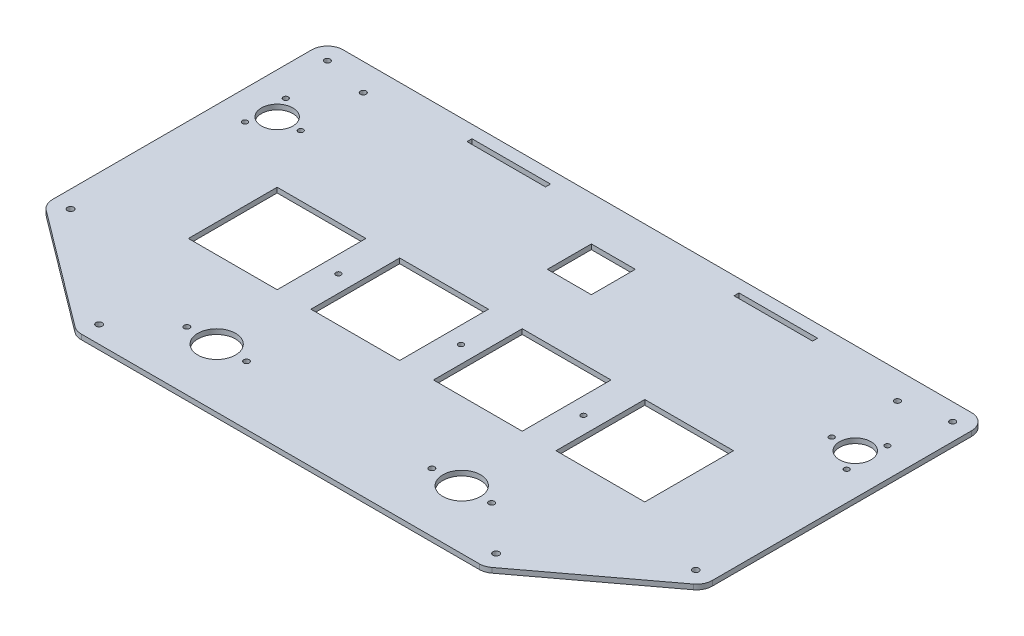
SolidWorks part; units mm, degrees
ref_plane "Front Plane" through (0, 0, 0) normal (0, 0, 1) x (1, 0, 0)
ref_plane "Top Plane" through (0, 0, 0) normal (0, 1, 0) x (1, 0, 0)
ref_plane "Right Plane" through (0, 0, 0) normal (1, 0, 0) x (0, 0, -1)
sketch "Sketch1" plane through (0, 0, 0) normal (0, 1, 0) x (1, 0, 0)
  line L0 (210, 240) -> (210, 0) construction
  line L1 (0, 0) -> (420, 0)
  line L2 (0, 0) -> (0, 240)
  line L3 (0, 240) -> (420, 240)
  line L4 (420, 0) -> (420, 240)
  line L5 (62, 115) -> (124, 115) construction
  line L6 (193, 215) -> (227, 215) construction
  line L7 (193, 215) -> (193, 181) construction
  line L8 (193, 181) -> (227, 181) construction
  line L9 (227, 215) -> (227, 181) construction
  line L10 (62, 84) -> (124, 84) construction
  line L11 (62, 84) -> (62, 146) construction
  line L12 (62, 146) -> (124, 146) construction
  line L13 (124, 84) -> (124, 146) construction
  line L14 (93, 146) -> (93, 84) construction
  line L15 (124, 84) -> (140, 84) construction
  line L16 (140, 84) -> (202, 84) construction
  line L17 (140, 84) -> (140, 146) construction
  line L18 (140, 146) -> (202, 146) construction
  line L19 (202, 84) -> (202, 146) construction
  line L20 (218, 84) -> (280, 84) construction
  line L21 (218, 84) -> (218, 146) construction
  line L22 (218, 146) -> (280, 146) construction
  line L23 (280, 84) -> (280, 146) construction
  line L24 (296, 84) -> (358, 84) construction
  line L25 (296, 84) -> (296, 146) construction
  line L26 (296, 146) -> (358, 146) construction
  line L27 (358, 84) -> (358, 146) construction
  line L28 (202, 84) -> (218, 84) construction
  line L29 (280, 84) -> (296, 84) construction
  line L30 (193, 198) -> (227, 198) construction
  line L31 (132, 84) -> (132, 54) construction
  line L32 (107, 21) -> (157, 21) construction
  line L33 (107, 21) -> (107, 54) construction
  line L34 (107, 54) -> (157, 54) construction
  line L35 (157, 21) -> (157, 54) construction
  line L36 (107, 37.5) -> (157, 37.5) construction
  line L37 (313, 21) -> (313, 54) construction
  line L38 (313, 54) -> (263, 54) construction
  line L39 (263, 21) -> (263, 54) construction
  line L40 (313, 21) -> (263, 21) construction
  line L41 (41, 182) -> (26, 182) construction
  line L42 (18.5, 194.9904) -> (18.5, 169.0096) construction
  line L43 (113, 37.5) -> (132, 37.5) construction
  line L44 (132, 37.5) -> (151, 37.5) construction
  line L45 (199.25, 143.25) -> (142.75, 143.25)
  line L46 (64.75, 143.25) -> (121.25, 143.25)
  line L47 (64.75, 143.25) -> (64.75, 86.75)
  line L48 (64.75, 86.75) -> (121.25, 86.75)
  line L49 (121.25, 143.25) -> (121.25, 86.75)
  line L50 (64.75, 143.25) -> (121.25, 86.75) construction
  line L51 (64.75, 86.75) -> (121.25, 143.25) construction
  line L52 (142.75, 143.25) -> (142.75, 86.75)
  line L53 (199.25, 86.75) -> (142.75, 86.75)
  line L54 (199.25, 143.25) -> (199.25, 86.75)
  line L55 (355.25, 86.75) -> (298.75, 86.75)
  line L56 (298.75, 143.25) -> (298.75, 86.75)
  line L57 (355.25, 143.25) -> (298.75, 143.25)
  line L58 (355.25, 143.25) -> (355.25, 86.75)
  line L59 (220.75, 143.25) -> (220.75, 86.75)
  line L60 (220.75, 86.75) -> (277.25, 86.75)
  line L61 (277.25, 143.25) -> (277.25, 86.75)
  line L62 (220.75, 143.25) -> (277.25, 143.25)
  line L64 (196, 212) -> (224, 212)
  line L65 (196, 212) -> (196, 184)
  line L66 (196, 184) -> (224, 184)
  line L67 (224, 212) -> (224, 184)
  line L68 (196, 212) -> (224, 184) construction
  line L69 (196, 184) -> (224, 212) construction
  circle A0 centre (26, 182) radius 15 construction
  circle A1 centre (41, 182) radius 1.65
  circle A2 centre (18.5, 169.0096) radius 1.65
  circle A3 centre (18.5, 194.9904) radius 1.65
  circle A4 centre (26, 182) radius 10
  circle A5 centre (132, 37.5) radius 12
  circle A6 centre (113, 37.5) radius 1.8
  circle A7 centre (151, 37.5) radius 1.8
  circle A8 centre (394, 182) radius 15 construction
  circle A9 centre (401.5, 194.9904) radius 1.65
  circle A10 centre (379, 182) radius 1.65
  circle A11 centre (394, 182) radius 10
  circle A12 centre (401.5, 169.0096) radius 1.65
  circle A13 centre (307, 37.5) radius 1.8
  circle A14 centre (269, 37.5) radius 1.8
  circle A15 centre (288, 37.5) radius 12
  point P11 (210, 215)
  point P20 (93, 115)
  point P58 (26, 182)
  point P63 (93, 115)
  point P80 (210, 198)
  dimension "D14" = 30
  dimension "D17" = 24
  dimension "D18" = 3.6
  dimension "D22" = 20
  dimension "D23" = 3.3
  dimension "D1" = 240
  dimension "D2" = 420
  dimension "D3" = 34
  dimension "D4" = 62
  dimension "D5" = 115
  dimension "D6" = 117
  dimension "D7" = 16
  dimension "D8" = 42
  dimension "D9" = 33
  dimension "D10" = 50
  dimension "D11" = 30
  dimension "D12" = 36
  dimension "D13" = 36
  dimension "D15" = 15
  dimension "D19" = 19
  dimension "D20" = 56.5
  dimension "D21" = 28
  dimension "D16" = 3
extrude "Boss-Extrude1" add sketch "Sketch1" along normal blind 3.175
sketch "Sketch2" plane through (0, 3.175, 0) normal (0, 1, 0) x (1, 0, 0)
  line L0 (0, 60) -> (0, 0)
  line L1 (0, 240) -> (0, 0) construction
  line L2 (0, 0) -> (80, 0)
  line L3 (0, 0) -> (420, 0) construction
  line L4 (80, 0) -> (0, 60)
  line L5 (420, 60) -> (420, 0)
  line L6 (420, 0) -> (420, 240) construction
  line L7 (420, 0) -> (340, 0)
  line L8 (340, 0) -> (420, 60)
  dimension "D1" = 80
  dimension "D2" = 60
extrude "Cut-Extrude1" cut sketch "Sketch2" against normal blind 10
fillet "Fillet1" radius 10 6 edges at (0, 1.5875, -60) (340, 1.5875, 0) (420, 1.5875, -240) (420, 1.5875, -60) (80, 1.5875, 0) (0, 1.5875, -240)
sketch "Sketch5" plane through (0, 3.175, 0) normal (0, 1, 0) x (1, 0, 0)
  line L0 (210, 240) -> (210, 0) construction
  line L1 (410, 240) -> (10, 240) construction
  line L2 (83.3333, 0) -> (336.6667, 0) construction
  line L3 (11, 65.5) -> (83.6667, 11) construction
  line L4 (77.3333, 2) -> (4, 57) construction
  line L5 (1.0557, 60.5279) -> (120, 120) construction
  line L6 (80.1711, 0.5132) -> (120, 120) construction
  line L7 (2.9289, 237.0711) -> (11, 229) construction
  line L8 (11, 229) -> (40, 229) construction
  line L9 (199.25, 115) -> (220.75, 115) construction
  line L10 (199.25, 86.75) -> (199.25, 143.25) construction
  line L11 (220.75, 143.25) -> (220.75, 86.75) construction
  line L12 (199.25, 115) -> (64.75, 115) construction
  line L13 (64.75, 143.25) -> (64.75, 86.75) construction
  line L14 (220.75, 115) -> (355.25, 115) construction
  line L15 (355.25, 86.75) -> (355.25, 143.25) construction
  line L16 (40, 229) -> (40, 222.825) construction
  circle A0 centre (11, 229) radius 1.83
  circle A2 centre (11, 65.5) radius 2
  circle A3 centre (83.6667, 11) radius 2
  arc A4 (0, 65) -> (4, 57) centre (10, 65) ccw construction
  arc A5 (77.3333, 2) -> (83.3333, 0) centre (83.3333, 10) ccw construction
  arc A6 (10, 240) -> (0, 230) centre (10, 230) ccw construction
  circle A9 centre (409, 65.5) radius 2
  circle A10 centre (336.3333, 11) radius 2
  circle A11 centre (210, 115) radius 1.66
  circle A12 centre (132, 115) radius 1.66
  circle A13 centre (288, 115) radius 1.66
  circle A14 centre (40, 222.825) radius 1.83
  circle A15 centre (380, 222.825) radius 1.83
  circle A16 centre (409, 229) radius 1.83
  point P26 (83.3333, 10)
  point P27 (10, 65)
  point P38 (10, 230)
  dimension "D2" = 4
  dimension "D5" = 3.32
  dimension "D7" = 3.66
  dimension "D1" = 11
  dimension "D3" = 11
  dimension "D4" = 29
  dimension "D6" = 6.175
extrude "Cut-Extrude2" cut sketch "Sketch5" against normal up to surface (3.175 mm away) up to face at (210, 0, -99.1853)
sketch "Sketch6" plane through (0, 3.175, 0) normal (0, 1, 0) x (1, 0, 0)
  line L0 (0, 230) -> (0, 65) construction
  line L1 (0, 228.825) -> (420, 228.825) construction
  line L2 (0, 228.825) -> (0, 232)
  line L3 (0, 232) -> (420, 232) construction
  line L4 (420, 228.825) -> (420, 232) construction
  line L5 (420, 65) -> (420, 230) construction
  line L6 (410, 240) -> (10, 240) construction
  line L7 (83.3333, 0) -> (336.6667, 0) construction
  line L8 (100, 232) -> (150, 232)
  line L9 (100, 232) -> (100, 228.825)
  line L10 (100, 228.825) -> (150, 228.825)
  line L11 (150, 232) -> (150, 228.825)
  line L12 (270, 232) -> (320, 232)
  line L13 (270, 232) -> (270, 228.825)
  line L14 (270, 228.825) -> (320, 228.825)
  line L15 (320, 232) -> (320, 228.825)
  line L16 (416, 57) -> (342.6667, 2) construction
  line L17 (73.3333, 5) -> (346.6667, 5) construction
  line L18 (73.3333, 5) -> (73.3333, 8.175)
  line L19 (73.3333, 8.175) -> (346.6667, 8.175) construction
  line L20 (346.6667, 5) -> (346.6667, 8.175) construction
  line L21 (77.3333, 2) -> (4, 57) construction
  line L23 (210, 5) -> (210, 0) construction
  line L24 (185, 8.175) -> (235, 8.175)
  line L25 (185, 8.175) -> (185, 5)
  line L26 (185, 5) -> (235, 5)
  line L27 (235, 8.175) -> (235, 5)
  dimension "D1" = 8
  dimension "D2" = 3.175
  dimension "D3" = 5
  dimension "D4" = 50
  dimension "D5" = 50
  dimension "D6" = 50
  dimension "D7" = 100
  dimension "D8" = 100
extrude "Cut-Extrude3" cut sketch "Sketch6" against normal up to surface (3.175 mm away) contours L8 L11 L10 L9 | L12 L15 L14 L13 up to face at (210, 0, -116.66)
